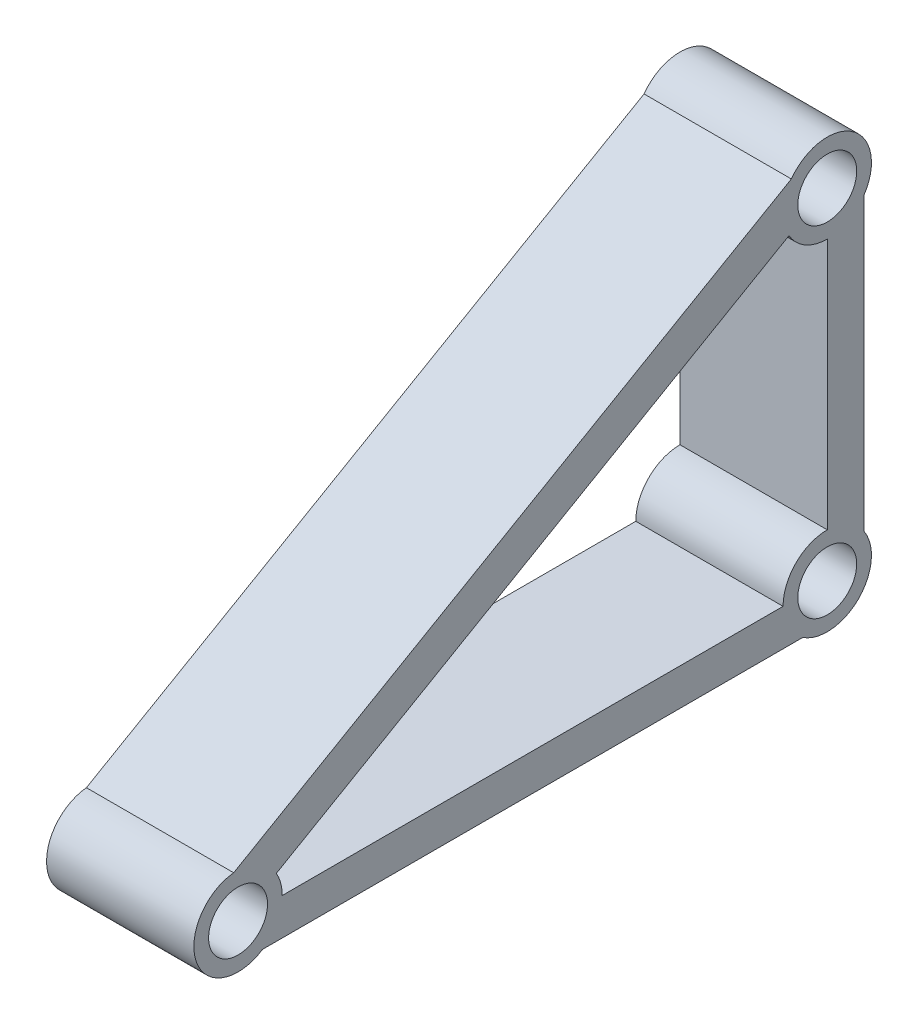
SolidWorks part; units mm, degrees
material "Thornel VCB-20 Carbon Cloth"
ref_plane "Front Plane" through (0, 0, 0) normal (0, 0, 1) x (1, 0, 0)
ref_plane "Top Plane" through (0, 0, 0) normal (0, 1, 0) x (1, 0, 0)
ref_plane "Right Plane" through (0, 0, 0) normal (1, 0, 0) x (0, 0, -1)
sketch "Sketch2" plane through (0, 0, 0) normal (1, 0, 0) x (0, 0, -1)
  line L0 (1528.6955, 519.1525) -> (1528.6955, 177.2722)
  line L2 (1476.734, 549.1525) -> (780.657, 147.2722)
  line L3 (722.7516, 176.9771) -> (1479.9615, 614.1525)
  line L4 (761.8617, 67.2722) -> (1495.5292, 67.2722)
  line L5 (1578.6955, 545.9862) -> (1578.6955, 150.4385)
  line L6 (1468.6955, 117.2722) -> (788.6955, 117.2722)
  line L7 (780.657, 147.2722) -> (728.6955, 117.2722) construction
  line L8 (728.6955, 117.2722) -> (788.6955, 117.2722) construction
  line L9 (1528.6955, 177.2722) -> (1528.6955, 117.2722) construction
  line L10 (1528.6955, 117.2722) -> (1468.6955, 117.2722) construction
  line L11 (1476.734, 549.1525) -> (1528.6955, 579.1525) construction
  line L12 (1528.6955, 579.1525) -> (1528.6955, 519.1525) construction
  line L13 (1479.9615, 614.1525) -> (1502.7147, 564.1525) construction
  arc A0 (780.657, 147.2722) -> (788.6955, 117.2722) centre (728.6955, 117.2722) ccw
  arc A1 (1528.6955, 519.1525) -> (1476.734, 549.1525) centre (1528.6955, 579.1525) ccw
  arc A2 (1468.6955, 117.2722) -> (1528.6955, 177.2722) centre (1528.6955, 117.2722) ccw
  circle A3 centre (728.6955, 117.2722) radius 40
  circle A4 centre (1528.6955, 579.1525) radius 40
  circle A5 centre (1528.6955, 117.2722) radius 40
  arc A6 (788.6955, 117.2722) -> (780.657, 147.2722) centre (728.6955, 117.2722) ccw
  arc A7 (1468.6955, 117.2722) -> (1528.6955, 177.2722) centre (1528.6955, 117.2722) cw
  arc A8 (1476.734, 549.1525) -> (1528.6955, 519.1525) centre (1528.6955, 579.1525) ccw
  dimension "D3" = 120
  dimension "D7" = 80
  dimension "D2" = 800
  dimension "D1" = 90
  dimension "D5" = 30
  dimension "D6" = 50
  dimension "D8" = 50
  dimension "D4" = 50
extrude "Boss-Extrude1" add sketch "Sketch2" along normal blind 200 contours A2 L6 A0 L4 | A1 L3 A0 L2 | A2 L5 A1 L0 | A0 A6 A3 | A7 A2 A5 | A1 A8 A4 region at (0, 348.2123, -1554.2791) region at (0, 528.6606, -1499.544) region at (0, 168.6446, -1556.2657) region at (0, 372.1927, -1114.8504) region at (0, 91.9722, -1128.6955) region at (0, 132.3622, -785.0118)
equation "\"controlAngle\" = 30deg"
equation "\"baseLength\"= 80cm"
equation "\"D2@Sketch2\"=\"baseLength\""
equation "\"D3@Sketch2\"=1.5*\"HoleMountDiameter@PrintingPress.Assembly\""
equation "\"D7@Sketch2\"=\"HoleMountDiameter@PrintingPress.Assembly\""
equation "\"D5@Sketch2\"=\"controlAngle\""
equation "\"D8@Sketch2\"=0.5*\"RivetLength@PrintingPress.Assembly\""
equation "\"D4@Sketch2\"=0.5*\"RivetLength@PrintingPress.Assembly\""
equation "\"D1@Boss-Extrude1\"=2*\"RivetLength@PrintingPress.Assembly\""
